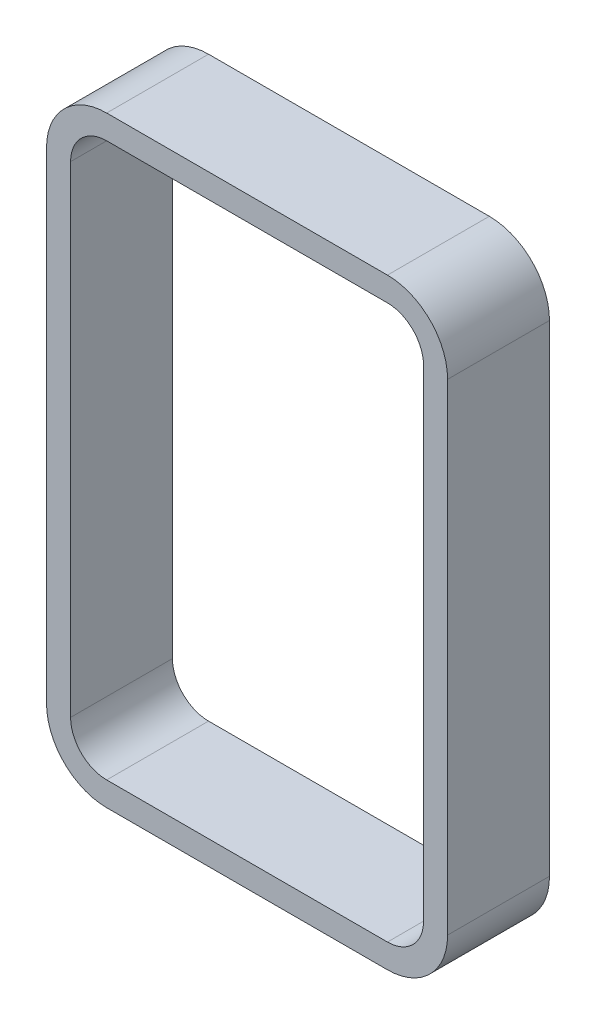
SolidWorks part; units mm, degrees
ref_plane "Front Plane" through (0, 0, 0) normal (0, 0, 1) x (1, 0, 0)
ref_plane "Top Plane" through (0, 0, 0) normal (0, 1, 0) x (1, 0, 0)
ref_plane "Right Plane" through (0, 0, 0) normal (1, 0, 0) x (0, 0, -1)
sketch "Sketch1" plane through (0, 0, 0) normal (0, 0, 1) x (1, 0, 0)
  line L0 (-35, 69) -> (35, 69)
  line L1 (-35, -75) -> (35, -75)
  line L2 (-50, -60) -> (-50, 60)
  line L3 (-35, 75) -> (35, 75)
  line L4 (50, -60) -> (50, 60)
  line L5 (-50, -75) -> (50, 75) construction
  line L6 (-50, 75) -> (50, -75) construction
  line L7 (44, -60) -> (44, 60)
  line L8 (-35, -69) -> (35, -69)
  line L9 (-44, -60) -> (-44, 60)
  arc A0 (-50, 60) -> (-35, 75) centre (-35, 60) cw
  arc A1 (35, 75) -> (50, 60) centre (35, 60) cw
  arc A2 (-35, -75) -> (-50, -60) centre (-35, -60) cw
  arc A3 (35, -75) -> (50, -60) centre (35, -60) ccw
  arc A4 (-44, 60) -> (-35, 69) centre (-35, 60) cw
  arc A5 (35, 69) -> (44, 60) centre (35, 60) cw
  arc A6 (35, -69) -> (44, -60) centre (35, -60) ccw
  arc A7 (-35, -69) -> (-44, -60) centre (-35, -60) cw
  point P0 (0, 0)
  dimension "D2" = 15
  dimension "Thickness" = 6
extrude "BaseSection" add sketch "Sketch1" along normal mid plane 25.4
equation "\"D2@Sketch1\" = \"Thickness@Sketch1\" * (  (IIf(\"Thickness@Sketch1\">3, 1.5, 1))  + 1 ) "
